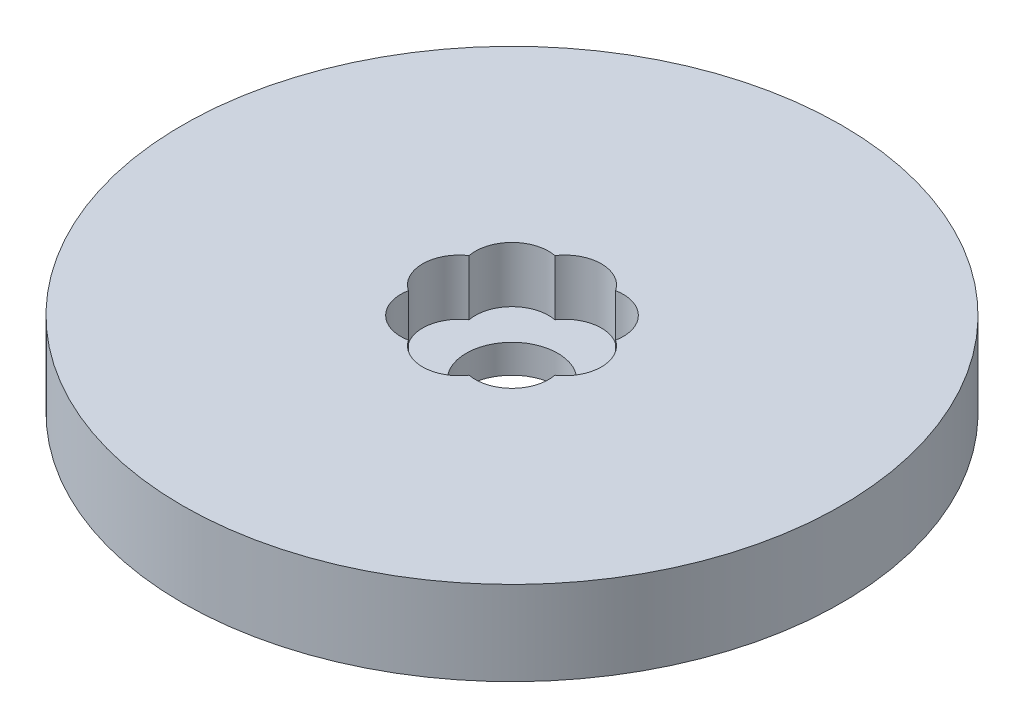
SolidWorks part; units mm, degrees
ref_plane "Front Plane" through (0, 0, 0) normal (0, 0, 1) x (1, 0, 0)
ref_plane "Top Plane" through (0, 0, 0) normal (0, 1, 0) x (1, 0, 0)
ref_plane "Right Plane" through (0, 0, 0) normal (1, 0, 0) x (0, 0, -1)
sketch "Sketch1" plane through (0, 0, 0) normal (0, 1, 0) x (1, 0, 0)
  circle A0 centre (0, 0) radius 90
  dimension "FLANGE_OD" = 180
extrude "Boss-Extrude1" add sketch "Sketch1" along normal blind 23
sketch "Sketch2" plane through (0, 0, 0) normal (0, 1, 0) x (1, 0, 0)
  circle A0 centre (0, 0) radius 12.5
  dimension "BORE_D" = 25
extrude "Cut-Extrude1" cut sketch "Sketch2" along normal through all
sketch "Sketch3" plane through (0, 23, 0) normal (0, 1, 0) x (1, 0, 0)
  circle A0 centre (0, 0) radius 14.4076 construction
  circle A1 centre (-14.4076, 0) radius 10
  dimension "BOLT_D" = 20
  dimension "BOLT_PCD" = 28.8152
extrude "Cut-Extrude2" cut sketch "Sketch3" against normal blind 15.1938
pattern_circular "CirPattern1" count 8 over 360 about axis through (0, 0, 0) along (0, 1, 0) of "Cut-Extrude2"
